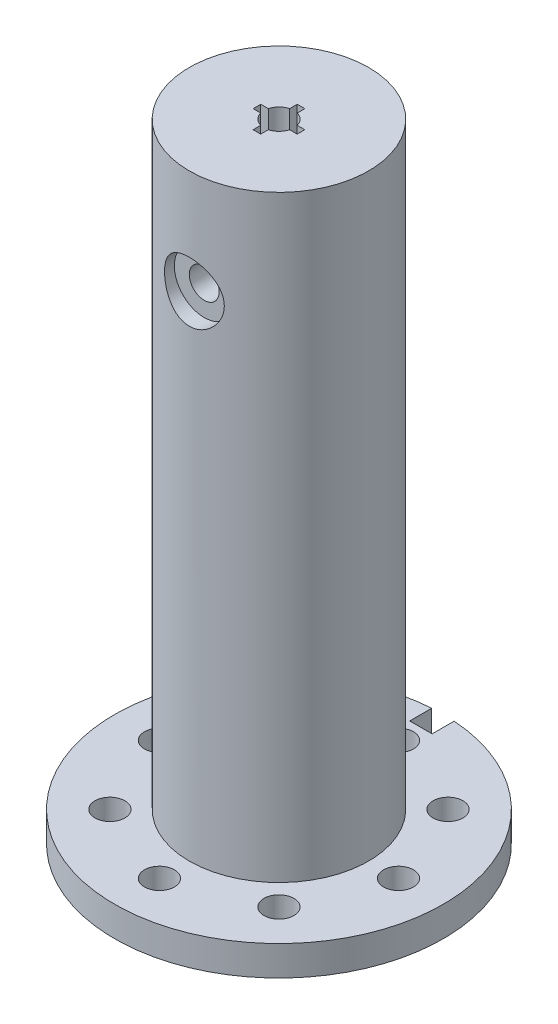
SolidWorks part; units mm, degrees
ref_plane "Front Plane" through (0, 0, 0) normal (0, 0, 1) x (1, 0, 0)
ref_plane "Top Plane" through (0, 0, 0) normal (0, 1, 0) x (1, 0, 0)
ref_plane "Right Plane" through (0, 0, 0) normal (1, 0, 0) x (0, 0, -1)
sketch "Sketch1" plane through (0, 0, 0) normal (0, 1, 0) x (1, 0, 0)
  circle A0 centre (0, 0) radius 11
  circle A1 centre (0, 8) radius 1
  circle A2 centre (5.6569, 5.6569) radius 1
  circle A3 centre (8, 0) radius 1
  circle A4 centre (5.6569, -5.6569) radius 1
  circle A5 centre (0, -8) radius 1
  circle A6 centre (-5.6569, -5.6569) radius 1
  circle A7 centre (-8, 0) radius 1
  circle A8 centre (-5.6569, 5.6569) radius 1
  point P22 (0, 0)
  dimension "D1" = 22
  dimension "D2" = 2
  dimension "D6" = 8
  dimension "D3" = 8
  dimension "D5" = 8
  dimension "D4" = 8
extrude "Boss-Extrude1" add sketch "Sketch1" along normal blind 2
sketch "Sketch2" plane through (0, 2, 0) normal (0, 1, 0) x (1, 0, 0)
  circle A0 centre (0, 0) radius 4
  dimension "D1" = 8
extrude "Cut-Extrude1" cut sketch "Sketch2" against normal through all
ref_plane "Plane1" through (0, 0, 0) normal (0, 1, 0) x (1, 0, 0)
sketch "Sketch3" plane through (0, 0, 0) normal (0, 1, 0) x (1, 0, 0)
  circle A0 centre (0, 0) radius 5
  circle A1 centre (0, 0) radius 11
  dimension "D1" = 10
  dimension "D2" = 22
sketch "Sketch4" plane through (0, 2, 0) normal (0, 1, 0) x (1, 0, 0)
  line L1 (-0.75, 12.5) -> (0.75, 12.5)
  line L2 (-0.75, 12.5) -> (-0.75, 9.5)
  line L3 (-0.75, 9.5) -> (0.75, 9.5)
  line L4 (0.75, 12.5) -> (0.75, 9.5)
  line L5 (-0.75, 12.5) -> (0.75, 9.5) construction
  line L6 (-0.75, 9.5) -> (0.75, 12.5) construction
  circle A0 centre (0, 0) radius 11 construction
  point P0 (0, 11)
  dimension "D1" = 1.5
  dimension "D2" = 3
extrude "Cut-Extrude3" cut sketch "Sketch4" against normal blind 4
sketch "Sketch5" plane through (0, 2, 0) normal (0, 1, 0) x (1, 0, 0)
  circle A0 centre (0, 0) radius 4
  circle A1 centre (0, 0) radius 6
  dimension "D1" = 8
  dimension "D2" = 12
extrude "Boss-Extrude2" add sketch "Sketch5" along normal blind 20 contours A1 | A0
sketch "Sketch6" plane through (0, 22, 0) normal (0, 1, 0) x (1, 0, 0)
  line L0 (-0.255, 0.9669) -> (0.255, 0.9669)
  line L1 (-0.255, 0.9669) -> (-0.255, 1.4769)
  line L2 (0.255, 0.9669) -> (0.255, 1.4769)
  line L3 (-0.255, 1.4769) -> (0.255, 1.4769)
  line L4 (-0.254, -0.9672) -> (0.254, -0.9672)
  line L5 (-0.254, -0.9672) -> (-0.254, -1.4752)
  line L6 (0.254, -0.9672) -> (0.254, -1.4752)
  line L7 (-0.254, -1.4752) -> (0.254, -1.4752)
  line L8 (0.9672, 0.254) -> (0.9672, -0.254)
  line L9 (0.9672, 0.254) -> (1.4752, 0.254)
  line L10 (0.9672, -0.254) -> (1.4752, -0.254)
  line L11 (1.4752, 0.254) -> (1.4752, -0.254)
  line L12 (-0.9672, 0.254) -> (-0.9672, -0.254)
  line L13 (-0.9672, 0.254) -> (-1.4752, 0.254)
  line L14 (-0.9672, -0.254) -> (-1.4752, -0.254)
  line L15 (-1.4752, 0.254) -> (-1.4752, -0.254)
  circle A0 centre (0, 0) radius 1
  circle A1 centre (0, 0) radius 4
  circle A2 centre (0, 0) radius 6
  circle M4 centre (0, 0) radius 6
  circle M5 centre (0, 0) radius 4
  dimension "D1" = 2
  dimension "D4" = 8
  dimension "D5" = 12
  dimension "D2" = 0.51
  dimension "D3" = 0.51
  dimension "D6" = 0.508
  dimension "D7" = 0.508
  dimension "D8" = 0.508
  dimension "D9" = 0.508
  dimension "D10" = 0.508
  dimension "D11" = 0.508
extrude "Boss-Extrude3" add sketch "Sketch6" along normal blind 20 contours A0 L1 L3 L2 M5 | M4 M5 region at (-3.8869, 22, 0) region at (-5.8303, 22, 0)
sketch "Sketch7" plane through (0, 0, 0) normal (0, 0, 1) x (1, 0, 0)
  line L0 (11, 0) -> (-11, 0) construction
  circle A0 centre (0, 35) radius 1
  dimension "D1" = 2
  dimension "D2" = 35
extrude "Cut-Extrude4" cut sketch "Sketch7" against normal blind 1 and the other way blind 5
ref_plane "Plane2" through (0, 0, 6) normal (0, 0, 1) x (1, 0, 0)
sketch "Sketch8" plane through (0, 0, 6) normal (0, 0, 1) x (1, 0, 0)
  circle A0 centre (0, 35) radius 2
  dimension "D1" = 4
extrude "Cut-Extrude5" cut sketch "Sketch8" against normal blind 1
